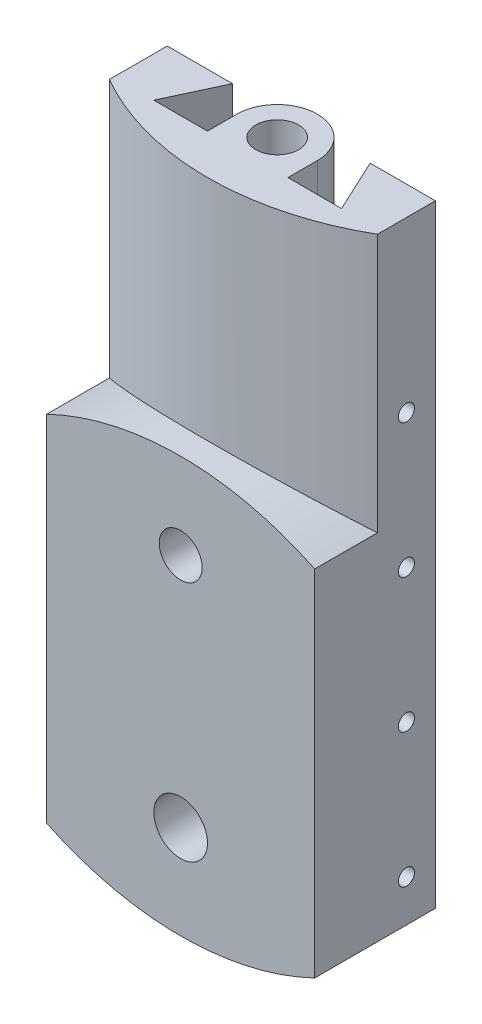
SolidWorks part; units mm, degrees
material "AISI 4130 Steel, normalized at 870C"
ref_plane "Front Plane" through (0, 0, 0) normal (0, 0, 1) x (1, 0, 0)
ref_plane "Top Plane" through (0, 0, 0) normal (0, 1, 0) x (1, 0, 0)
ref_plane "Right Plane" through (0, 0, 0) normal (1, 0, 0) x (0, 0, -1)
sketch "Sketch1" plane through (0, 0, 0) normal (0, 1, 0) x (1, 0, 0)
  line L0 (-50, 0) -> (50, 0)
  line L1 (50, 0) -> (50, 45)
  line L2 (50, 45) -> (25.6738, 45)
  line L3 (25.6738, 45) -> (35, 25)
  line L4 (35, 25) -> (15, 25)
  line L5 (0, 0) -> (0, 36) construction
  line L6 (15, 25) -> (15, 36)
  line L7 (-15, 36) -> (-15, 25)
  line L8 (-15, 25) -> (-35, 25)
  line L9 (-35, 25) -> (-25.6738, 45)
  line L10 (-25.6738, 45) -> (-50, 45)
  line L11 (-50, 45) -> (-50, 0)
  line L12 (-15, 25) -> (-15, 23.5)
  line L13 (-15, 23.5) -> (15, 23.5)
  line L14 (15, 23.5) -> (15, 25)
  arc A0 (15, 36) -> (-15, 36) centre (0, 36) ccw
  circle A1 centre (0, 36) radius 8
  arc A2 (-50, 23.3975) -> (50, 23.3975) centre (0, 110) ccw
  point P11 (0, 0)
  dimension "D4" = 15
  dimension "D10" = 16
  dimension "D11" = 100
  dimension "D12" = 41
  dimension "D1" = 100
  dimension "D2" = 70
  dimension "D3" = 45
  dimension "D5" = 35
  dimension "D6" = 36
  dimension "D7" = 20
  dimension "D8" = 65
  dimension "D9" = 65
  dimension "D13" = 1.5
extrude "Boss-Extrude1" add sketch "Sketch1" against normal blind 25 contours L6 A0 L7 L12 L13 A1 L14 region at (-14.593, 0, -30.5)
extrude "Boss-Extrude2" add sketch "Sketch1<3>" against normal blind 240 contours L5 A2 L1 L2 L3 L4 L14 L13 | A2 L5 L13 L12 L8 L9 L10 L11 region at (-49.3897, 0, -34.1987) region at (0.6103, 0, -16.75)
sketch "Sketch1<3>" plane through (0, 0, 0) normal (0, 1, 0) x (1, 0, 0) same geometry as "Sketch1"
sketch "Sketch2" plane through (0, 0, 0) normal (0, 0, 1) x (1, 0, 0)
  line L0 (-50, -240) -> (-50, 0) construction
  line L1 (50, -240) -> (50, 0) construction
  line L2 (-50, -240) -> (50, -240) construction
  line L3 (50, -96.4384) -> (50, -228.5616)
  line L4 (-50, -96.4384) -> (-50, -228.5616)
  arc A2 (-50, -228.5616) -> (50, -228.5616) centre (0, -125) ccw
  arc A3 (-50, -96.4384) -> (50, -96.4384) centre (0, -200) cw
  dimension "D1" = 155
  dimension "D4" = 115
  dimension "D5" = 115
extrude "Boss-Extrude3" add sketch "Sketch2" against normal up to next
sketch "Sketch3" plane through (0, 0, 0) normal (0, 0, 1) x (1, 0, 0)
  line L0 (-50, -228.5616) -> (-50, -240)
  line L1 (-50, -240) -> (50, -240)
  line L2 (50, -240) -> (50, -228.5616)
  arc A0 (-50, -228.5616) -> (50, -228.5616) centre (0, -125) ccw construction
  arc A3 (-50, -228.5616) -> (50, -228.5616) centre (0, -125) ccw
  circle A6 centre (0, -117) radius 8
  circle A7 centre (0, -205) radius 10
  arc M3 (-50, -228.5616) -> (50, -228.5616) centre (0, -125) ccw
  dimension "D3" = 20
  dimension "D4" = 16
  dimension "D1" = 35
  dimension "D2" = 88
extrude "Cut-Extrude1" cut sketch "Sketch3" against normal through all contours A7 | L0 L1 M3 | L1 L2 M3 | A6 region at (-37.6277, -236.5999, 0) region at (37.6277, -236.5999, 0) region at (0, -205, 0)
sketch "Sketch4" plane through (50, 0, 0) normal (1, 0, 0) x (0, 0, -1)
  line L0 (34.1987, -216) -> (34.1987, 0) construction
  line L1 (23.3975, 0) -> (45, 0) construction
  circle A0 centre (34.1987, -63) radius 3
  circle A1 centre (34.1987, -113) radius 3
  circle A2 centre (34.1987, -163) radius 3
  circle A3 centre (34.1987, -213) radius 3
  dimension "D1" = 6
  dimension "D2" = 63
  dimension "D3" = 50
  dimension "D4" = 50
  dimension "D5" = 50
extrude "Cut-Extrude2" cut sketch "Sketch4" against normal through all
